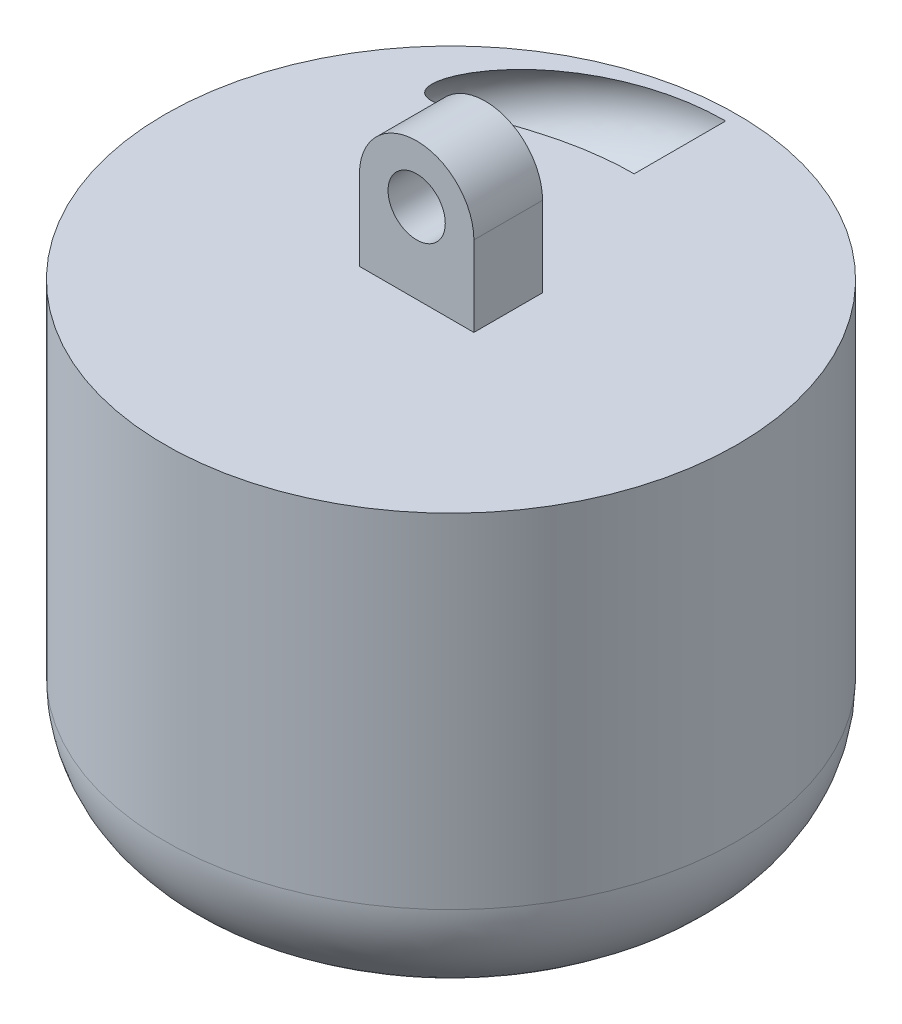
SolidWorks part; units mm, degrees
ref_plane "Front Plane" through (0, 0, 0) normal (0, 0, 1) x (1, 0, 0)
ref_plane "Top Plane" through (0, 0, 0) normal (0, 1, 0) x (1, 0, 0)
ref_plane "Right Plane" through (0, 0, 0) normal (1, 0, 0) x (0, 0, -1)
sketch "Sketch1" plane through (0, 0, 0) normal (0, 0, 1) x (1, 0, 0)
  line L0 (0, -2.25) -> (-2.5, -2.25)
  line L1 (-2.5, -2.25) -> (-2.5, 1.25)
  line L3 (2.5, 1.25) -> (2.5, -2.25)
  line L4 (2.5, -2.25) -> (0, -2.25)
  line L5 (0, -2.25) -> (0, 3.75) construction
  arc A2 (2.5, 1.25) -> (-2.5, 1.25) centre (0, 1.25) ccw
  circle A3 centre (0, 1.25) radius 1.25
  dimension "D1" = 2.5
  dimension "D2" = 6
  dimension "D3" = 2.5
extrude "Boss-Extrude1" add sketch "Sketch1" along normal blind 3
sketch "Sketch2" plane through (0, -2.25, 0) normal (0, -1, 0) x (1, 0, 0)
  line L0 (2.5, 0) -> (-2.5, 3) construction
  line L1 (-2.5, 0) -> (2.5, 3) construction
  circle A0 centre (0, 1.5) radius 12.5
  dimension "D1" = 25
extrude "Boss-Extrude2" add sketch "Sketch2" along normal blind 20
sketch "Sketch87" plane through (0, 0, 0) normal (1, 0, 0) x (0, 0, -1)
  line L2 (11, -22.25) -> (11, -2.25) construction
  circle A1 centre (8.5, -2.25) radius 2
  dimension "D1" = 2.5
sketch "Sketch88" plane through (0, -2.25, 0) normal (0, 1, 0) x (1, 0, 0)
  circle A0 centre (0, -1.5) radius 12.125
  dimension "D1" = 24.25
curve "Helix/Spiral4" pitch 14.5 height 10.875 radius 12.125 left hand yes centre (0, -2.25, 1.5) axis (0, -1, 0) start towards (-1, 0, 0)
sweep "Cut-Sweep24" cut profiles "Sketch87" path "Helix/Spiral4" align with end faces yes
ref_plane "Plane4" through (0, 0, -11) normal (0, 0, 1) x (1, 0, 0)
ref_plane "Plane5" through (12.5, 0, 0) normal (1, 0, 0) x (0, 0, -1)
fillet "Fillet1" radius 5 1 edges at (12.5, -22.25, 1.5)
ref_axis "Axis1" through (0, -17.25, 1.5) along (0, 1, 0)
